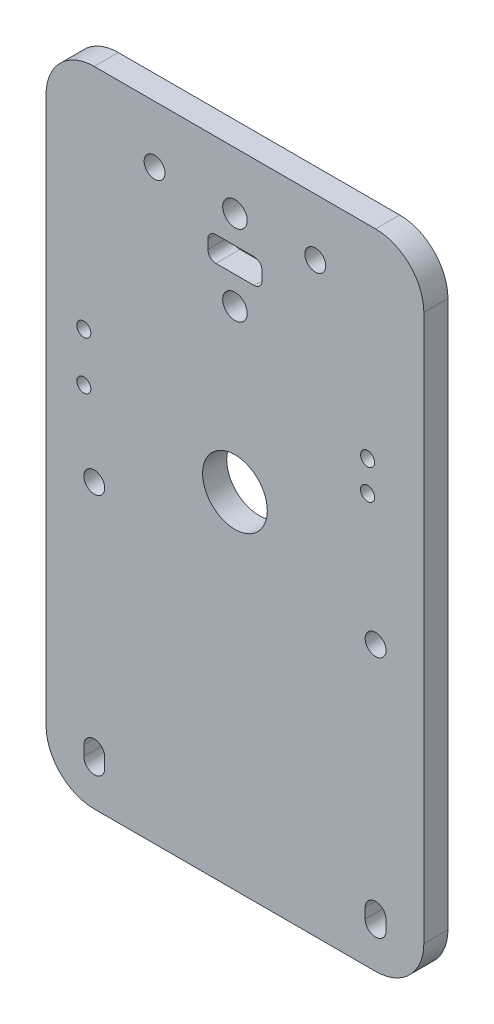
SolidWorks part; units mm, degrees
material "Acrylic (Medium-high impact)"
ref_plane "Спереди" through (0, 0, 0) normal (0, 0, 1) x (1, 0, 0)
ref_plane "Сверху" through (0, 0, 0) normal (0, 1, 0) x (1, 0, 0)
ref_plane "Справа" through (0, 0, 0) normal (1, 0, 0) x (0, 0, -1)
sketch "Model" plane through (0, 0, 0) normal (0, 0, 1) x (1, 0, 0)
  line L5 (0, 170.1561) -> (0, 0) construction
  line L24 (-35, 37.2847) -> (-35, 78.8619) construction
  line L25 (-31.4983, 12.5) -> (-38.4, 12.5) construction
  line L26 (-31.4983, 10) -> (-38.4, 10) construction
  line L27 (-35, 12.5) -> (-35, 10) construction
  line L28 (-32.4, 12.5) -> (-32.4, 10)
  line L29 (-37.6, 12.5) -> (-37.6, 10)
  line L40 (31.4983, 10) -> (38.4, 10) construction
  line L41 (31.4983, 12.5) -> (38.4, 12.5) construction
  line L42 (35, 37.2847) -> (35, 78.8619) construction
  line L43 (35, 12.5) -> (35, 10) construction
  line L44 (32.4, 12.5) -> (32.4, 10)
  line L45 (37.6, 12.5) -> (37.6, 10)
  line L47 (-26.0102, 145.8) -> (26.0946, 145.8) construction
  line L50 (-20, 133.6948) -> (-20, 127.8457) construction
  line L51 (-38.85, 70.45) -> (-29.8907, 70.45) construction
  line L53 (-16.3166, 125.8) -> (17.7871, 125.8) construction
  line L58 (38.85, 70.45) -> (29.8907, 70.45) construction
  line L4875 (-35, 160) -> (35, 160)
  line L4882 (47, 148) -> (47, 12)
  line L4889 (35, 0) -> (-35, 0)
  line L4896 (-47, 12) -> (-47, 148)
  line L6648 (-6.75, 138.9) -> (6.75, 138.9)
  line L6649 (6.75, 138.9) -> (6.75, 132.7)
  line L6650 (6.75, 132.7) -> (-6.75, 132.7)
  line L6651 (-6.75, 132.7) -> (-6.75, 138.9)
  arc A0 (-47, 12) -> (-35, 0) centre (-35, 12) ccw
  arc A1 (35, 0) -> (47, 12) centre (35, 12) ccw
  arc A2 (47, 148) -> (35, 160) centre (35, 148) ccw
  arc A3 (-35, 160) -> (-47, 148) centre (-35, 148) ccw
  arc A13 (-32.4, 12.5) -> (-37.6, 12.5) centre (-35, 12.5) ccw
  arc A14 (-37.6, 10) -> (-32.4, 10) centre (-35, 10) ccw
  arc A19 (32.4, 12.5) -> (37.6, 12.5) centre (35, 12.5) cw
  arc A20 (37.6, 10) -> (32.4, 10) centre (35, 10) cw
  circle A29 centre (0, 145.8) radius 3.05
  circle A30 centre (-20, 145.8) radius 2.6
  circle A31 centre (20, 145.8) radius 2.6
  circle A32 centre (-35, 70.45) radius 2.6
  circle A33 centre (0, 125.8) radius 3.05
  circle A36 centre (35, 70.45) radius 2.6
  point P0 (-6.75, 135.8)
  point P17 (0, 0)
  point P77 (-35, 11.25)
  point P114 (35, 11.25)
  dimension "D29" = 5.2
  dimension "D30" = 5.2
  dimension "D33" = 5.2
  dimension "D35" = 6.1
  dimension "D5" = 5.2
  dimension "D2" = 70
  dimension "D3" = 160
  dimension "D15" = 12
  dimension "D16" = 2.5
  dimension "D17" = 10
  dimension "D18" = 5.2
  dimension "D25" = 14.2
  dimension "D34" = 20
  dimension "D42" = 6.2
  dimension "D9" = 70
  dimension "D10" = 57.95
  dimension "D6" = 20
  dimension "D7" = 20
  dimension "D8" = 13.5
  dimension "D11" = 10
extrude "Base" add sketch "Model" along normal blind 6 contours L4875 A3 L4896 A0 L4889 A1 L4882 A2 L45 A20 L44 A19 region at (0, 79.6161, 0)
sketch "Эскиз1" plane through (0, 0, 0) normal (0, 0, -1) x (-1, 0, 0)
  line L0 (35, 160) -> (-35, 160) construction
  line L1 (0, 160) -> (0, 146.8198) construction
  circle A0 centre (0, 85.8) radius 8.05
  dimension "D2" = 16.1
  dimension "D1" = 74.2
extrude "BearingHole" cut sketch "Эскиз1" against normal blind 10
sketch "Sketch1" plane through (0, 0, 6) normal (0, 0, 1) x (1, 0, 0)
  line L0 (-35, 160) -> (35, 160) construction
  line L1 (47, 148) -> (47, 12) construction
  circle A0 centre (33, 109.5) radius 1.75
  circle A1 centre (33, 102) radius 1.75
  dimension "D1" = 3.5
  dimension "D3" = 7.5
  dimension "D4" = 50.5
  dimension "D5" = 14
extrude "SensorMount" cut sketch "Sketch1" against normal blind 10
sketch "Sketch3" plane through (0, 0, 0) normal (0, 0, -1) x (-1, 0, 0)
  line L0 (-35, 0) -> (35, 0) construction
  line L1 (47, 12) -> (47, 148) construction
  circle A0 centre (37.6, 90.0886) radius 1.75
  circle A1 centre (37.6, 102.0886) radius 1.75
  dimension "D3" = 3.5
  dimension "D4" = 90.0886
  dimension "D1" = 12
  dimension "D2" = 9.4
extrude "CableMount" cut sketch "Sketch3" against normal blind 10
fillet "FilletCableSlot" radius 2 4 edges at (6.75, 138.9, 3) (-6.75, 138.9, 3) (-6.75, 132.7, 3) (6.75, 132.7, 3)
ref_plane "Plane1" through (0, 40.225, 0) normal (0, -1, 0) x (-1, 0, 0)
equation "\"D11@Model\"=\"D34@Model\"/2"
